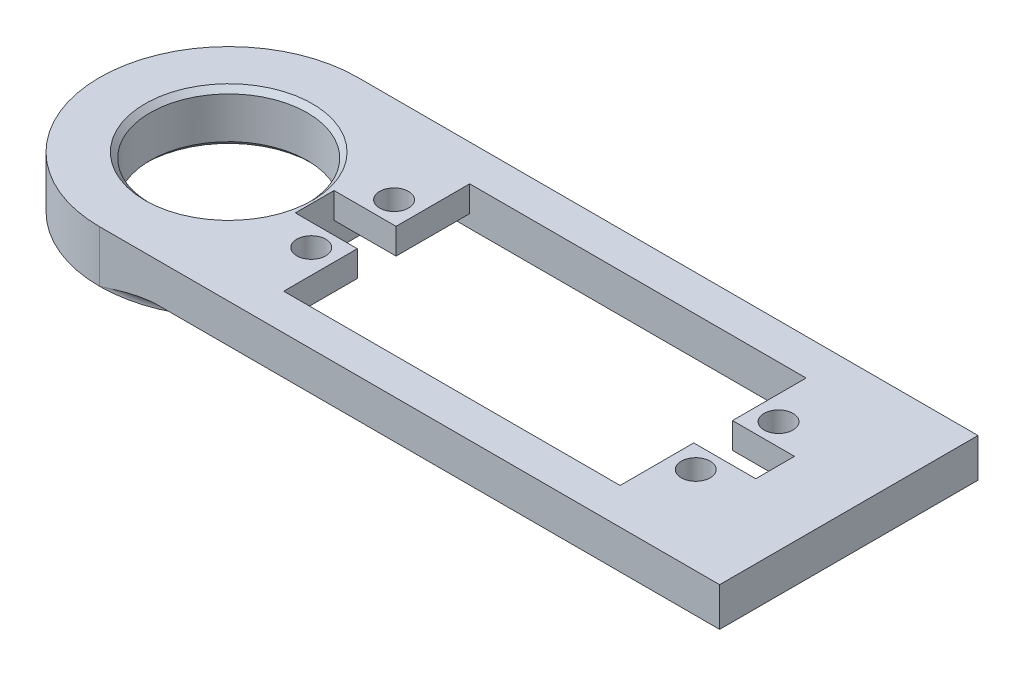
SolidWorks part; units mm, degrees
ref_plane "Front Plane" through (0, 0, 0) normal (0, 0, 1) x (1, 0, 0)
ref_plane "Top Plane" through (0, 0, 0) normal (0, 1, 0) x (1, 0, 0)
ref_plane "Right Plane" through (0, 0, 0) normal (1, 0, 0) x (0, 0, -1)
sketch "Sketch1" plane through (0, 0, 0) normal (0, 1, 0) x (1, 0, 0)
  line L0 (12.7, 15.875) -> (76.2, 15.875)
  line L1 (76.2, 15.875) -> (76.2, -15.875)
  line L2 (76.2, -15.875) -> (12.7, -15.875)
  line L3 (12.7, 15.875) -> (12.7, -15.875) construction
  line L4 (0, 0) -> (12.7, 0) construction
  line L5 (0, 15.875) -> (12.7, 15.875)
  line L6 (0, -15.875) -> (12.7, -15.875)
  arc A1 (0, 15.875) -> (0, -15.875) centre (0, 0) ccw
  dimension "D2" = 12.7
  dimension "D3" = 63.5
  dimension "D4" = 15.875
  dimension "D5" = 31.75
extrude "Boss-Extrude1" add sketch "Sketch1" along normal blind 4.7625
sketch "Sketch4" plane through (0, 0, 0) normal (0, -1, 0) x (1, 0, 0)
  circle A0 centre (0, 0) radius 15.875
extrude "Boss-Extrude2" add sketch "Sketch4" along normal blind 1.5875
sketch "Sketch5" plane through (0, -1.5875, 0) normal (0, -1, 0) x (1, 0, 0)
  circle A0 centre (0, 0) radius 9.652
  dimension "D1" = 19.304
extrude "Cut-Extrude4" cut sketch "Sketch5" against normal through all
sketch "Sketch2" plane through (0, 4.7625, 0) normal (0, 1, 0) x (1, 0, 0)
  point P0 (0, 0)
  line B0 (15.233, -5.085) -> (62.477, 5.085) construction
  line B1 (18.185, -11.43) -> (18.185, 11.43) construction
  line B2 (18.185, -11.43) -> (59.525, -11.43)
  line B3 (59.525, -11.43) -> (59.525, 11.43) construction
  line B4 (18.185, 11.43) -> (59.525, 11.43)
  line B5 (18.185, -11.43) -> (59.525, 11.43) construction
  line B6 (59.525, -11.43) -> (18.185, 11.43) construction
  line B7 (18.185, 0) -> (28.575, 0) construction
  circle B8 centre (15.233, 5.085) radius 1.778
  circle B9 centre (15.233, -5.085) radius 1.778
  circle B10 centre (62.477, 5.085) radius 1.778
  circle B11 centre (62.477, -5.085) radius 1.778
  line B12 (18.185, -11.43) -> (18.185, -2.3813)
  line B13 (18.185, 11.43) -> (18.185, 2.3812)
  arc B14 (18.185, 2.3812) -> (18.185, -2.3813) centre (18.185, 0) ccw construction
  line B15 (18.185, -2.3813) -> (10.565, -2.3813)
  line B16 (10.565, -2.3813) -> (10.565, 2.3812)
  line B17 (10.565, 2.3812) -> (18.185, 2.3812)
  line B18 (59.525, 2.3813) -> (67.145, 2.3813)
  line B19 (67.145, 2.3813) -> (67.145, -2.3812)
  line B20 (67.145, -2.3812) -> (59.525, -2.3812)
  line B21 (59.525, 11.43) -> (59.525, 2.3813)
  line B22 (59.525, -2.3812) -> (59.525, -11.43)
  dimension "D1" = 28.575
sketch_block_instance "Servo Mount ABS-2"
sketch_block "Servo Mount ABS" parameters "D5"=3.556, "D7"=1.8773, "D1"=22.86, "D2"=41.34, "D3"=10.17, "D4"=47.244, "D6"=10.39, "D8"=7.7865, "D9"=5.4364
extrude "Cut-Extrude2" cut sketch "Sketch2" against normal through all
chamfer "Chamfer1" distance 0.635 angle 45 2 edges at (0, 4.7625, 9.652) (0, -1.5875, -9.652)
sketch "Sketch3" plane through (0, 0, 0) normal (0, -1, 0) x (1, 0, 0)
  line L0 (18.185, 11.43) -> (59.525, 11.43) construction
  line L1 (10.565, 11.43) -> (67.145, 11.43)
  line L2 (10.565, 11.43) -> (10.565, -11.43)
  line L3 (10.565, -11.43) -> (67.145, -11.43)
  line L4 (67.145, 11.43) -> (67.145, -11.43)
  line L5 (59.525, -11.43) -> (18.185, -11.43) construction
  line L6 (67.145, 2.3812) -> (67.145, -2.3813) construction
  line L7 (10.565, -2.3812) -> (10.565, 2.3813) construction
extrude "Cut-Extrude3" cut sketch "Sketch3" against normal blind 1.5875 and the other way through all
fillet "Fillet1" radius 1.5875 1 edges
fillet "Fillet2" radius 1.5875 3 edges at (67.145, 0.7937, -11.43) (10.565, 0, 11.43) (10.565, 0, -11.43)
fillet "Fillet3" radius 1.5875 2 edges at (67.145, 0.7937, 11.43)
